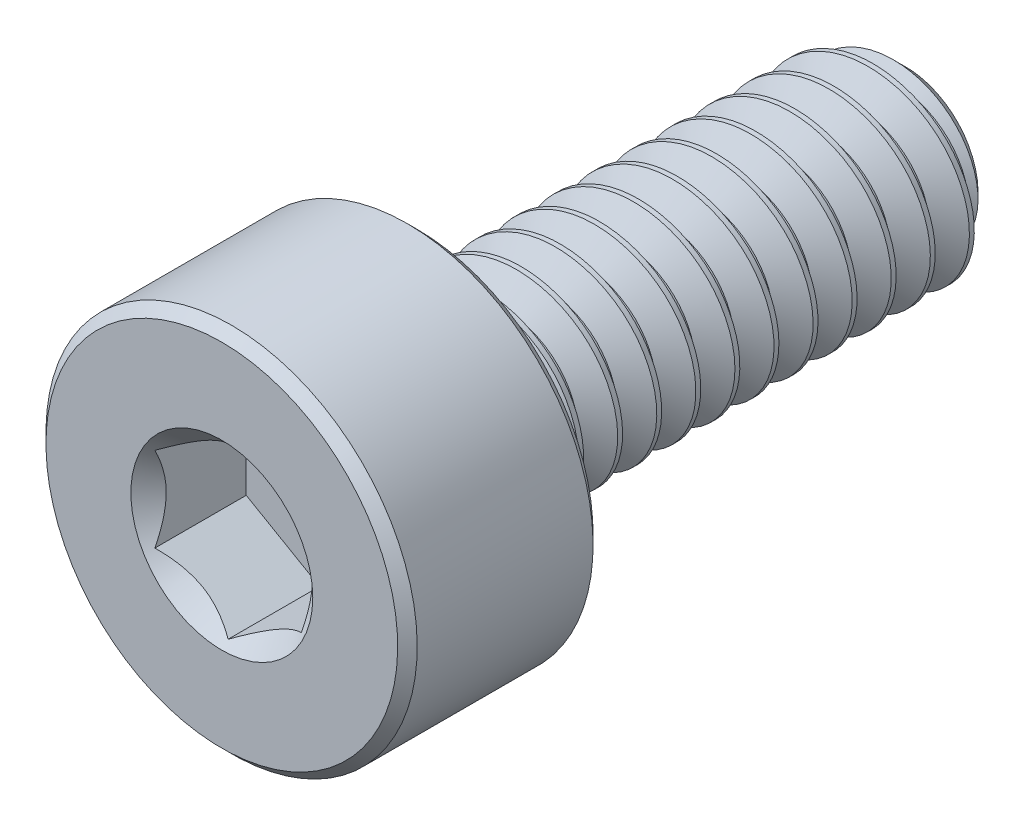
SolidWorks part; units mm, degrees
ref_plane "Front Plane" through (0, 0, 0) normal (0, 0, 1) x (1, 0, 0)
ref_plane "Top Plane" through (0, 0, 0) normal (0, 1, 0) x (1, 0, 0)
ref_plane "Right Plane" through (0, 0, 0) normal (1, 0, 0) x (0, 0, -1)
sketch "Sketch1" plane through (0, 0, 0) normal (1, 0, 0) x (0, 0, -1)
  line L0 (-3.5, 0) -> (3.5, 0) construction
  line L1 (3.5, 0) -> (3.5, 0.7402) construction
  line L2 (3.5, 0.7402) -> (3.2402, 1) construction
  line L3 (3.2402, 1) -> (3.2, 1) construction
  line L4 (3.2, 1) -> (-1.5, 1) construction
  line L5 (-1.5, 1) -> (-1.5, 1.9) construction
  line L6 (-1.5, 1.9) -> (-3.5, 1.9) construction
  line L7 (-3.5, 1.9) -> (-3.5, 0) construction
  line L8 (3.5, 0.7402) -> (3.5, 1) construction
  line L9 (3.475, 1.0433) -> (3.675, 0.6969) construction
  line L10 (3.675, 0.6969) -> (3.875, 1.0433) construction
  line L11 (3.875, 1.0433) -> (3.475, 1.0433) construction
  line L12 (3.675, 1.0433) -> (3.675, 1) construction
  line L13 (3.675, 0.6969) -> (3.675, 0.7402) construction
  line L14 (3.65, 0.7402) -> (3.7, 0.7402) construction
  line L15 (3.5, 1) -> (3.85, 1) construction
  line L16 (3.4875, 1.0217) -> (3.8625, 1.0217) construction
  line L17 (3.5, 0) -> (3.5, -1) construction
  line L18 (-1.6, 1.9) -> (-1.5, 1.8) construction
  line L19 (-3.4, 1.9) -> (-3.5, 1.8) construction
  line L20 (-1.5, 1) -> (-1.5, 0) construction
  line L21 (-1.5, 0.5) -> (0.1667, 0.5) construction
  line L22 (0.1667, 0.5) -> (1.8333, 0.5) construction
  line L23 (1.8333, 0.5) -> (3.5, 0.5) construction
  line L24 (0.1667, 0.5) -> (0.1667, 1) construction
  line L25 (0.1667, 1) -> (0.1667, 1.9) construction
  line L26 (1.8333, 0.5) -> (1.8333, 1.9) construction
  point P0 (-3.5, 0.75)
  point P3 (2.5, 1)
  point P4 (0, 0)
  point P18 (1.8333, 1)
  point P22 (3.675, 0.7402)
  point P24 (3.2, 1)
  point P25 (3.675, 1)
  point P28 (3.675, 1.0217)
  point P29 (2.5, -1)
  point P30 (0.1667, 1)
  point P31 (-2.5, 1.9)
  point P37 (-1.85, 1.9)
  point P38 (-3.35, 1.9)
  point P45 (0.1667, 0.5)
  point P46 (1.8333, 0.5)
  dimension "D2" = 0.05
  dimension "D7" = 0.1
  dimension "D8" = 0.1
  dimension "D9" = 0.1
  dimension "D10" = 0.05
  dimension "D11" = 0.25
  dimension "Drive Size" = 1.5
  dimension "Head Diameter" = 3.8
  dimension "Head Height" = 2
  dimension "Thread Pitch" = 0.4
  dimension "Thread Size" = 2
  dimension "Length" = 5
  dimension "D12" = 0.3
  dimension "D4" = 1
  dimension "D3" = 45
sketch "Sketch2" plane through (0, 0, 0) normal (1, 0, 0) x (0, 0, -1)
  line L0 (-3.5, 0) -> (-3.5, 1.8)
  line L1 (-3.4, 1.9) -> (-1.6, 1.9)
  line L2 (-1.5, 1.8) -> (-1.5, 1.1)
  line L4 (3.2402, 1) -> (3.5, 0.7402)
  line L5 (3.5, 0.7402) -> (3.5, 0)
  line L6 (-1.5, 1.9) -> (-3.5, 1.9) construction
  line L7 (3.5, 0) -> (-3.5, 0)
  line L8 (-3.4, 1.9) -> (-3.5, 1.8) construction
  line L10 (-3.4, 1.9) -> (-3.5, 1.8)
  line L14 (-1.6, 1.9) -> (-1.5, 1.8) construction
  line L16 (-1.6, 1.9) -> (-1.5, 1.8)
  line L17 (-1.5, 1) -> (-1.5, 1.9) construction
  line L19 (-1.4, 1) -> (3.2402, 1)
  line L20 (3.2, 1) -> (-1.5, 1) construction
  arc A1 (-1.5, 1.1) -> (-1.4, 1) centre (-1.4, 1.1) ccw
revolve "Revolve1" add sketch "Sketch2" angle 360 about L7
sketch "Sketch3" plane through (0, 0, 3.5) normal (0, 0, 1) x (1, 0, 0)
  line L1 (0.75, -0.433) -> (0.75, 0.433)
  line L2 (0.75, 0.433) -> (0, 0.866)
  line L3 (0, 0.866) -> (-0.75, 0.433)
  line L4 (-0.75, 0.433) -> (-0.75, -0.433)
  line L5 (-0.75, -0.433) -> (0, -0.866)
  line L6 (0, -0.866) -> (0.75, -0.433)
  circle A0 centre (0, 0) radius 0.75 construction
  circle A1 centre (0, 0) radius 1.9 construction
  circle A2 centre (0, 0) radius 1.9 construction
  circle A3 centre (0, 0) radius 0.866 construction
  point P13 (0, 0)
  dimension "D1" = 1.7321
extrude "Cut-Extrude1" cut sketch "Sketch3" against normal offset from surface (1 mm away) 1 up to face at (0, 1.8, 1.5)
sketch "Sketch4" plane through (0, 0, 3.5) normal (0, 0, 1) x (1, 0, 0)
  circle A0 centre (0, 0) radius 0.931
  dimension "D1" = 1.862
extrude "Cut-Extrude2" cut sketch "Sketch4" against normal up to vertex (1 mm away) draft 45 up to point (0, 1.9, 2.5)
sketch "Sketch11" plane through (0, 0, 0) normal (1, 0, 0) x (0, 0, -1)
  line L0 (-3.5, 0) -> (3.5, 0) construction
  line L1 (-3.5, 0) -> (3.5, 0) construction
  line L2 (-0.5625, 0) -> (-0.5625, 1) construction
  line L3 (3.2, 1) -> (-1.5, 1) construction
  line L4 (2.5625, 0) -> (2.5625, 1) construction
  line L6 (3.5, 0.7402) -> (3.5, 1) construction
  point P2 (-0.5625, 0)
  point P3 (2.5625, 0)
  dimension "D1" = 0.9375
  dimension "D2" = 0.9375
sketch "Sketch6" plane through (0, 0, -3.5) normal (0, 0, -1) x (-1, 0, 0)
  circle A0 centre (0, 0) radius 1
curve "Helix/Spiral1" pitch 0.4 height 5.4 radius 1 centre (0, 0, -3.5) axis (0, 0, 1) start towards (0, 1, 0)
sketch "Sketch10" plane through (0, 0, 0) normal (1, 0, 0) x (0, 0, -1)
  line L0 (-1.4, -1.9) -> (-1.4, 1.9)
  line L5 (-3.5, 0) -> (3.5, 0) construction
  line L6 (-1.4, 1) -> (-1.4, -1) construction
  point P3 (-1.4, 0)
split "Split1" trim tools "Sketch10" bodies to split 106 resulting bodies 114 115
sketch "Sketch7" plane through (0, 0, 0) normal (1, 0, 0) x (0, 0, -1)
  line L0 (3.4875, 1.0217) -> (3.8625, 1.0217)
  line L1 (3.8625, 1.0217) -> (3.7, 0.7402)
  line L2 (3.7, 0.7402) -> (3.65, 0.7402)
  line L3 (3.65, 0.7402) -> (3.4875, 1.0217)
sweep "Cut-Sweep1" cut profiles "Sketch7" path "Helix/Spiral1" align with end faces yes
sketch "Sketch8" plane through (0, 0, 0) normal (1, 0, 0) x (0, 0, -1)
  line L0 (-1.5, 0) -> (-1.5, 1)
  line L1 (-1.4, -1) -> (-1.4, 1) construction
  line L2 (-1.5, 1) -> (-1.4, 1)
  line L4 (-1.4, 1) -> (-0.8226, 0)
  line L5 (-0.8226, 0) -> (-1.5, 0)
  line L6 (3.2, 1) -> (-1.5, 1) construction
  line L7 (-3.5, 0) -> (3.5, 0) construction
  dimension "D1" = 60
revolve "Revolve2" add sketch "Sketch8" angle 360 about L5
equation "\"D2@Sketch1\" = \"Thread Pitch@Sketch1\" / 8"
equation "\"D4@Helix/Spiral1\" = \"Thread Pitch@Sketch1\""
equation "\"D7@Sketch1\" = \"Head Height@Sketch1\" * .05"
equation "\"D8@Sketch1\"=\"D7@Sketch1\""
equation "\"D9@Sketch1\"=\"D7@Sketch1\""
equation "\"D10@Sketch1\"=\"D7@Sketch1\"/2"
equation "\"D11@Sketch1\"=\"D10@Sketch1\"*5"
equation "\"D4@Sketch1\"=\"Thread Pitch@Sketch1\"*2.5"
equation "\"D12@Sketch1\"=\"Thread Pitch@Sketch1\"*.75"
equation "\"D3@Helix/Spiral1\"=\"Length@Sketch1\"+\"Thread Pitch@Sketch1\""
equation "\"D3@Sketch2\"=\"Thread Size@Sketch1\"*0.05"
equation "\"D1@Sketch11\"=\"Length@Sketch1\"*0.1875"
equation "\"D2@Sketch11\"=\"D1@Sketch11\""
equation "\"D1@Sketch4\"=\"D1@Sketch3\"*1.075"
